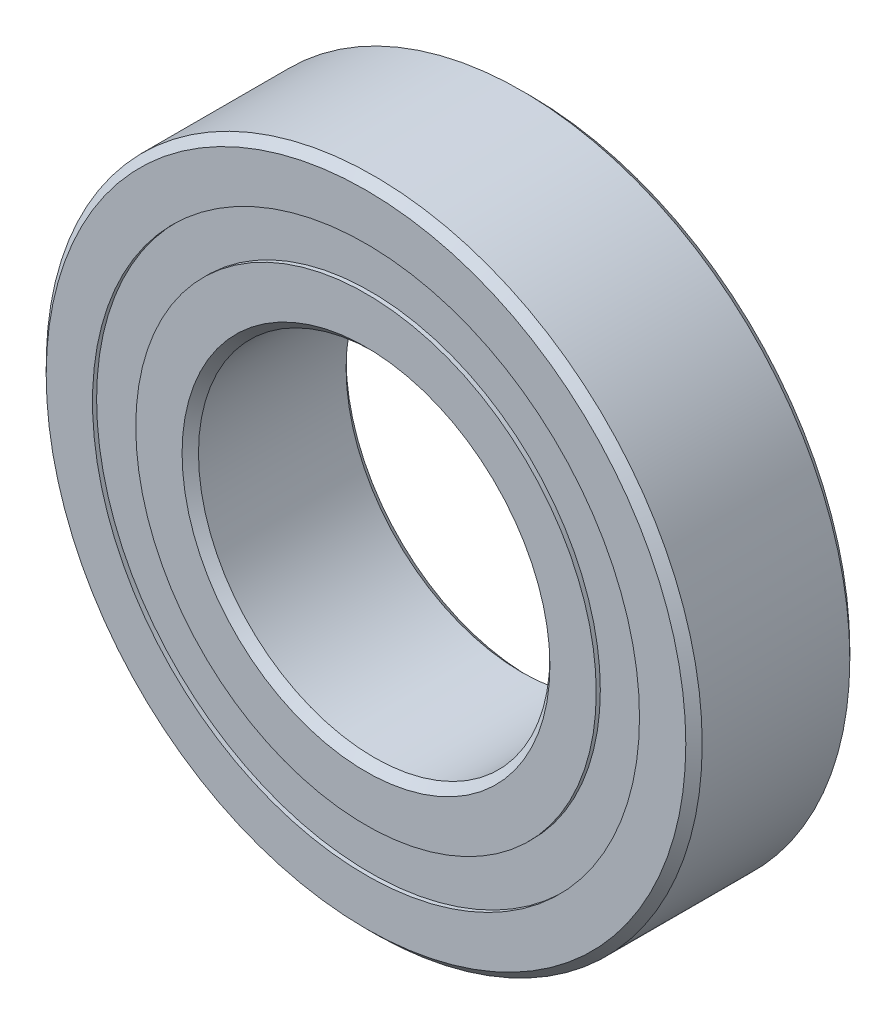
SolidWorks part; units mm, degrees
ref_plane "Front Plane" through (0, 0, 0) normal (0, 0, 1) x (1, 0, 0)
ref_plane "Top Plane" through (0, 0, 0) normal (0, 1, 0) x (1, 0, 0)
ref_plane "Right Plane" through (0, 0, 0) normal (1, 0, 0) x (0, 0, -1)
sketch "Sketch1" plane through (0, 0, 0) normal (0, 0, 1) x (1, 0, 0)
  circle A0 centre (0, 0) radius 14 construction
  circle A1 centre (0, 0) radius 7.5 construction
  dimension "OD" = 28
  dimension "Shaft Dia" = 15
sketch "Sketch2" plane through (0, 0, 0) normal (1, 0, 0) x (0, 0, -1)
  line L0 (-3.5, 0) -> (3.5, 0) construction
  line L1 (0, 14) -> (0, -14) construction
  line L2 (3.15, 14) -> (-3.15, 14) construction
  line L3 (-3.15, 14) -> (-3.5, 13.65) construction
  line L4 (-3.5, 13.65) -> (-3.5, 11.6731) construction
  line L5 (-3.5, 11.6731) -> (-1.5556, 11.6731) construction
  line L6 (3.5, 11.6731) -> (1.5556, 11.6731) construction
  line L7 (3.5, 13.65) -> (3.5, 11.6731) construction
  line L8 (3.15, 14) -> (3.5, 13.65) construction
  line L9 (0, 14) -> (0, 10.75) construction
  line L10 (0, 10.75) -> (0, 7.5) construction
  line L11 (3.5, 10.75) -> (-3.5, 10.75) construction
  line L12 (-3.5, 7.85) -> (-3.5, 9.8269) construction
  line L13 (-3.15, 7.5) -> (-3.5, 7.85) construction
  line L14 (3.15, 7.5) -> (-3.15, 7.5) construction
  line L15 (3.15, 7.5) -> (3.5, 7.85) construction
  line L16 (3.5, 7.85) -> (3.5, 9.8269) construction
  line L17 (3.5, 9.8269) -> (1.5556, 9.8269) construction
  line L18 (-3.5, 9.8269) -> (-1.5556, 9.8269) construction
  arc A0 (-1.5556, 11.6731) -> (1.5556, 11.6731) centre (0, 10.75) cw construction
  arc A1 (-1.5556, 9.8269) -> (1.5556, 9.8269) centre (0, 10.75) ccw construction
  point P14 (0, 7.5)
  point P18 (0, 10.75)
  dimension "D1" = 45
  dimension "D2" = 0.35
  dimension "D3" = 3.1111
  dimension "D4" = 0.9231
  dimension "Width" = 7
sketch "Sketch6" plane through (0, 0, 0) normal (1, 0, 0) x (0, 0, -1)
  line L0 (-3.5, 13.65) -> (-3.5, 11.6731) construction
  line L1 (-3.15, 14) -> (-3.5, 13.65) construction
  line L2 (3.15, 14) -> (-3.15, 14) construction
  line L3 (3.15, 14) -> (3.5, 13.65) construction
  line L4 (3.5, 13.65) -> (3.5, 11.6731) construction
  line L5 (3.5, 11.6731) -> (1.5556, 11.6731) construction
  line L6 (-3.5, 11.6731) -> (-1.5556, 11.6731) construction
  line L7 (-3.5, 13.65) -> (-3.5, 11.6731)
  line L8 (-3.15, 14) -> (-3.5, 13.65)
  line L9 (3.15, 14) -> (-3.15, 14)
  line L10 (3.15, 14) -> (3.5, 13.65)
  line L11 (3.5, 13.65) -> (3.5, 11.6731)
  line L12 (3.5, 11.6731) -> (1.5556, 11.6731)
  line L13 (-3.5, 11.6731) -> (-1.5556, 11.6731)
  line L14 (-3.5, 7.85) -> (-3.5, 9.8269) construction
  line L15 (-3.15, 7.5) -> (-3.5, 7.85) construction
  line L16 (3.15, 7.5) -> (-3.15, 7.5) construction
  line L17 (3.15, 7.5) -> (3.5, 7.85) construction
  line L18 (3.5, 7.85) -> (3.5, 9.8269) construction
  line L19 (3.5, 9.8269) -> (1.5556, 9.8269) construction
  line L20 (-3.5, 9.8269) -> (-1.5556, 9.8269) construction
  line L21 (-3.5, 7.85) -> (-3.5, 9.8269)
  line L22 (-3.15, 7.5) -> (-3.5, 7.85)
  line L23 (3.15, 7.5) -> (-3.15, 7.5)
  line L24 (3.15, 7.5) -> (3.5, 7.85)
  line L25 (3.5, 7.85) -> (3.5, 9.8269)
  line L26 (3.5, 9.8269) -> (1.5556, 9.8269)
  line L27 (-3.5, 9.8269) -> (-1.5556, 9.8269)
  arc A0 (1.5556, 11.6731) -> (-1.5556, 11.6731) centre (0, 10.75) ccw construction
  arc A1 (1.5556, 11.6731) -> (-1.5556, 11.6731) centre (0, 10.75) ccw
  arc A2 (-1.5556, 9.8269) -> (1.5556, 9.8269) centre (0, 10.75) ccw construction
  arc A3 (-1.5556, 9.8269) -> (1.5556, 9.8269) centre (0, 10.75) ccw
revolve "Revolve1" add sketch "Sketch6" angle 360 about L0
sketch "Sketch4" plane through (0, 0, 0) normal (1, 0, 0) x (0, 0, -1)
  line L0 (-1.8088, 10.75) -> (1.8088, 10.75)
  arc A2 (-1.8088, 10.75) -> (1.8088, 10.75) centre (0, 10.75) cw
  arc A3 (1.5556, 11.6731) -> (-1.5556, 11.6731) centre (0, 10.75) ccw construction
revolve "Revolve2" add sketch "Sketch4" angle 360 about L0
ref_axis "Axis1" through (0, 0, -3.5) along (0, 0, 1)
pattern_circular "CirPattern1" count 12 every 30 about axis through (0, 0, -3.5) along (0, 0, 1) of bodies 104
sketch "Sketch5" plane through (0, 0, 0) normal (1, 0, 0) x (0, 0, -1)
  line L0 (-3.5, 11.6731) -> (-1.5556, 11.6731) construction
  line L1 (-3.325, 11.6731) -> (-1.8088, 11.6731)
  line L2 (-3.325, 11.6731) -> (-3.325, 9.8269)
  line L3 (-3.325, 9.8269) -> (-1.8088, 9.8269)
  line L4 (-1.8088, 11.6731) -> (-1.8088, 9.8269)
  line L6 (3.5, 11.6731) -> (1.5556, 11.6731) construction
  line L7 (3.325, 11.6731) -> (1.8088, 11.6731)
  line L8 (3.325, 11.6731) -> (3.325, 9.8269)
  line L9 (3.325, 9.8269) -> (1.8088, 9.8269)
  line L10 (1.8088, 11.6731) -> (1.8088, 9.8269)
  line L12 (-3.15, 14) -> (-3.5, 13.65) construction
  line L13 (-3.5, 9.8269) -> (-1.5556, 9.8269) construction
  line L14 (3.5, 9.8269) -> (1.5556, 9.8269) construction
  point P18 (-3.325, 13.825)
revolve "Revolve3" add sketch "Sketch5" angle 360 about L0
equation "\"D2@Sketch2\"= \"Width@Sketch2\" * .05"
equation "\"D3@Sketch2\"=\"Width@Sketch2\" / 2.25"
equation "\"D4@Sketch2\"= ( ( ( \"OD@Sketch1\" - \"Width@Sketch2\" ) / 2 ) / 3.25 ) / 3.5"
equation "\"D2@CirPattern1\" = 360/\"Balls@CirPattern1\""
